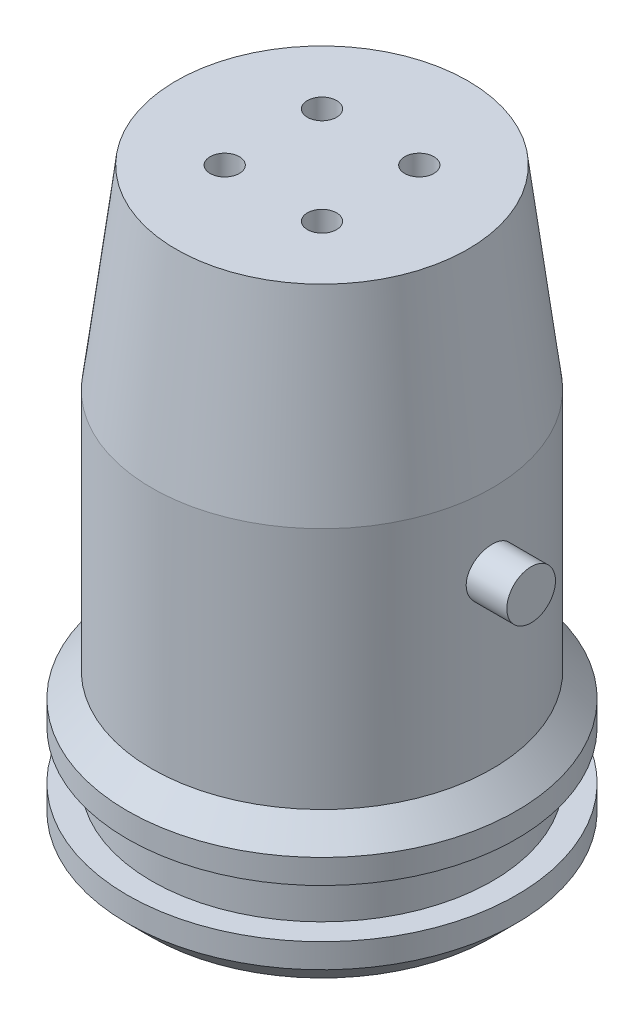
SolidWorks part; units mm, degrees
ref_plane "Front Plane" through (0, 0, 0) normal (0, 0, 1) x (1, 0, 0)
ref_plane "Top Plane" through (0, 0, 0) normal (0, 1, 0) x (1, 0, 0)
ref_plane "Right Plane" through (0, 0, 0) normal (1, 0, 0) x (0, 0, -1)
sketch "Sketch1" plane through (0, 0, 0) normal (0, 0, 1) x (1, 0, 0)
  line L0 (15, 0) -> (17.5, 0)
  line L1 (17.5, 0) -> (17.5, 40)
  line L2 (17.5, 40) -> (15, 60)
  line L3 (0, 0) -> (0, 103.4743) construction
  line L4 (15, 0) -> (15, 40)
  line L5 (15, 40) -> (12.875, 57)
  line L6 (12.875, 57) -> (0, 57)
  line L7 (0, 57) -> (0, 60)
  line L8 (0, 60) -> (15, 60)
  dimension "D1" = 35
  dimension "D2" = 3
  dimension "D3" = 60
  dimension "D4" = 40
  dimension "D5" = 30
revolve "Revolve1" add sketch "Sketch1" angle 360 about L3
ref_plane "Plane1" through (14, 0, 0) normal (1, 0, 0) x (0, 0, -1)
sketch "Sketch2" plane through (14, 0, 0) normal (1, 0, 0) x (0, 0, -1)
  line L0 (-17.5, 0) -> (17.5, 0) construction
  circle A0 centre (0, 32.5) radius 2.5
  dimension "D1" = 5
  dimension "D2" = 32.5
extrude "Boss-Extrude1" add sketch "Sketch2" along normal blind 7.5
ref_plane "Plane2" through (0, 5, 0) normal (0, 1, 0) x (1, 0, 0)
sketch "Sketch4" plane through (0, 5, 0) normal (0, 1, 0) x (1, 0, 0)
  circle A0 centre (0, 0) radius 17.5 construction
  circle A1 centre (0, 0) radius 17.5
  circle A2 centre (0, 0) radius 20
  dimension "D1" = 40
extrude "Boss-Extrude3" add sketch "Sketch4" against normal blind 2.5
ref_plane "Plane3" through (0, 10, 0) normal (0, 1, 0) x (1, 0, 0)
sketch "Sketch5" plane through (0, 10, 0) normal (0, 1, 0) x (1, 0, 0)
  circle A1 centre (0, 0) radius 20
  circle A2 centre (0, 0) radius 20
  circle A3 centre (0, 0) radius 17.5
  circle A4 centre (0, 0) radius 17.5
  dimension "D1" = 0
  dimension "D2" = 0
extrude "Boss-Extrude4" add sketch "Sketch5" along normal blind 2.5
sketch "Sketch6" plane through (0, 60, 0) normal (0, 1, 0) x (1, 0, 0)
  circle A0 centre (-5, 5) radius 1.5
  dimension "D1" = 3
  dimension "D2" = 5
  dimension "D3" = 5
extrude "Cut-Extrude1" cut sketch "Sketch6" against normal through all
pattern_circular "CirPattern1" count 4 every 90 about axis through (0, 0, 0) along (0, -1, 0) of "Cut-Extrude1"
sketch "Sketch7" plane through (0, 0, 0) normal (0, 0, 1) x (1, 0, 0)
  line L1 (-10, 37.5) -> (10, 37.5)
  line L2 (-10, 37.5) -> (-10, 27.5)
  line L3 (-10, 27.5) -> (10, 27.5)
  line L4 (10, 37.5) -> (10, 27.5)
  line L5 (0, 60) -> (0, 15) construction
  line L6 (15, 60) -> (-15, 60) construction
  line L7 (-17.5, 0) -> (17.5, 0) construction
  point P11 (0, 37.5)
  dimension "D1" = 20
  dimension "D2" = 10
  dimension "D3" = 27.5
extrude "Cut-Extrude2" cut sketch "Sketch7" against normal through all
chamfer "Chamfer1" distance 2.5 angle 45 2 edges at (0, 2.5, 17.5) (0, 12.5, 17.5)
